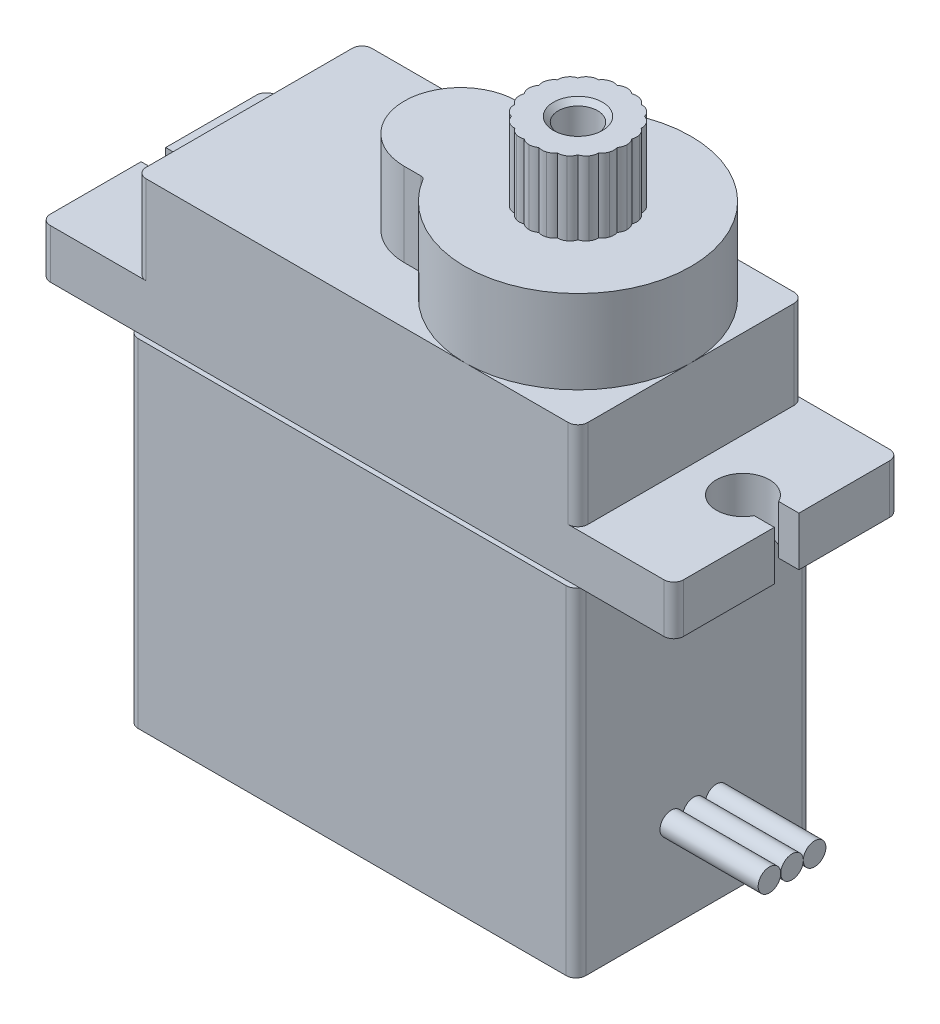
SolidWorks part; units mm, degrees
ref_plane "Ön Düzlem" through (0, 0, 0) normal (0, 0, 1) x (1, 0, 0)
ref_plane "Üst Düzlem" through (0, 0, 0) normal (0, 1, 0) x (1, 0, 0)
ref_plane "Sağ Düzlem" through (0, 0, 0) normal (1, 0, 0) x (0, 0, -1)
sketch "Sketch1" plane through (0, 0, 0) normal (0, 1, 0) x (1, 0, 0)
  line L1 (-11.4, -6) -> (11.4, -6)
  line L2 (-11.4, -6) -> (-11.4, 6)
  line L3 (-11.4, 6) -> (11.4, 6)
  line L4 (11.4, -6) -> (11.4, 6)
  line L5 (-11.4, -6) -> (11.4, 6) construction
  line L6 (-11.4, 6) -> (11.4, -6) construction
  point P0 (0, 0)
  dimension "D1" = 22.8
  dimension "D2" = 12
extrude "Boss-Extrude1" add sketch "Sketch1" along normal blind 17.2
sketch "Sketch2" plane through (0, 17.2, 0) normal (0, 1, 0) x (1, 0, 0)
  line L0 (-11.4, 6) -> (-11.4, -6) construction
  line L1 (-16.125, -5.75) -> (16.125, -5.75)
  line L2 (-16.125, -5.75) -> (-16.125, -0.625)
  line L3 (-16.125, 5.75) -> (16.125, 5.75)
  line L4 (16.125, -5.75) -> (16.125, -0.625)
  line L5 (-16.125, -5.75) -> (16.125, 5.75) construction
  line L6 (-16.125, 5.75) -> (16.125, -5.75) construction
  line L7 (0, -5.75) -> (0, 5.75) construction
  line L8 (-16.125, 0.625) -> (-16.125, 5.75)
  line L9 (-15.0966, 0.625) -> (-16.125, 0.625)
  line L10 (-15.0966, -0.625) -> (-16.125, -0.625)
  line L11 (-15.6108, 0.625) -> (-15.6108, -0.625) construction
  line L12 (15.0966, 0.625) -> (16.125, 0.625)
  line L13 (15.0966, -0.625) -> (16.125, -0.625)
  line L14 (16.125, 0.625) -> (16.125, 5.75)
  arc A0 (-15.0966, -0.625) -> (-15.0966, 0.625) centre (-13.9, 0) ccw
  arc A1 (15.0966, -0.625) -> (15.0966, 0.625) centre (13.9, 0) cw
  point P0 (0, 0)
  point P10 (-15.6108, 0)
  point P14 (0, 0)
  dimension "D5" = 2.7
  dimension "D1" = 11.5
  dimension "D2" = 32.25
  dimension "D3" = 4.725
  dimension "D4" = 2.5
  dimension "D6" = 1.25
extrude "Boss-Extrude2" add sketch "Sketch2" along normal blind 2.5
sketch "Sketch3" plane through (0, 19.7, 0) normal (0, 1, 0) x (1, 0, 0)
  line L0 (11.4, 5.75) -> (-11.4, 5.75) construction
  line L1 (-11.25, -5.75) -> (11.25, -5.75)
  line L2 (-11.25, -5.75) -> (-11.25, 5.75)
  line L3 (-11.25, 5.75) -> (11.25, 5.75)
  line L4 (11.25, -5.75) -> (11.25, 5.75)
  line L5 (-11.25, -5.75) -> (11.25, 5.75) construction
  line L6 (-11.25, 5.75) -> (11.25, -5.75) construction
  line L7 (-16.125, 5.75) -> (-16.125, 0.625) construction
  point P0 (0, 0)
  dimension "D1" = 22.5
  dimension "D2" = 4.875
extrude "Boss-Extrude3" add sketch "Sketch3" along normal blind 4.5
sketch "Sketch4" plane through (0, 24.2, 0) normal (0, 1, 0) x (1, 0, 0)
  line L0 (11.25, 5.75) -> (-11.25, 5.75) construction
  line L2 (-11.4, -5.75) -> (11.4, -5.75) construction
  line L4 (11.25, -5.75) -> (11.25, 5.75) construction
  line L5 (-0.475, 2.875) -> (0.378, 2.875)
  line L6 (-0.475, -2.875) -> (0.378, -2.875)
  arc A0 (0.5915, -2.9948) -> (0.5915, 2.9948) centre (5.5, 0) ccw
  arc A1 (-0.475, 2.875) -> (-0.475, -2.875) centre (-0.475, 0) ccw
  arc A2 (0.5915, -2.9948) -> (0.378, -2.875) centre (0.378, -3.125) ccw
  arc A3 (0.5915, 2.9948) -> (0.378, 2.875) centre (0.378, 3.125) cw
  dimension "D1" = 5.975
  dimension "D2" = 5.75
  dimension "D3" = 0.25
extrude "Boss-Extrude4" add sketch "Sketch4" along normal blind 4.25
sketch "Sketch5" plane through (0, 28.45, 0) normal (0, 1, 0) x (1, 0, 0)
  arc A1 (3.1357, 0.3745) -> (3.0053, 0) centre (3.5651, 0.015) ccw
  arc A2 (3.1357, -0.3745) -> (3.0053, 0) centre (3.5651, -0.015) cw
  circle A3 centre (5.5, 0) radius 2.375 construction
  arc A4 (3.3671, 1.0868) -> (3.1274, 0.7709) centre (3.6644, 0.6122) ccw
  arc A5 (3.1357, 0.3745) -> (3.1274, 0.7709) centre (3.6551, 0.5837) cw
  arc A6 (3.8073, 1.6927) -> (3.4817, 1.4664) centre (3.9434, 1.1495) ccw
  arc A7 (3.3671, 1.0868) -> (3.4817, 1.4664) centre (3.9258, 1.1252) cw
  arc A8 (4.4132, 2.1329) -> (4.0336, 2.0183) centre (4.3748, 1.5742) ccw
  arc A9 (3.8073, 1.6927) -> (4.0336, 2.0183) centre (4.3505, 1.5566) cw
  arc A10 (5.1255, 2.3643) -> (4.7291, 2.3726) centre (4.9163, 1.8449) ccw
  arc A11 (4.4132, 2.1329) -> (4.7291, 2.3726) centre (4.8878, 1.8356) cw
  arc A12 (5.8745, 2.3643) -> (5.5, 2.4947) centre (5.515, 1.9349) ccw
  arc A13 (5.1255, 2.3643) -> (5.5, 2.4947) centre (5.485, 1.9349) cw
  arc A14 (6.5868, 2.1329) -> (6.2709, 2.3726) centre (6.1122, 1.8356) ccw
  arc A15 (5.8745, 2.3643) -> (6.2709, 2.3726) centre (6.0837, 1.8449) cw
  arc A16 (7.1927, 1.6927) -> (6.9664, 2.0183) centre (6.6495, 1.5566) ccw
  arc A17 (6.5868, 2.1329) -> (6.9664, 2.0183) centre (6.6252, 1.5742) cw
  arc A18 (7.6329, 1.0868) -> (7.5183, 1.4664) centre (7.0742, 1.1252) ccw
  arc A19 (7.1927, 1.6927) -> (7.5183, 1.4664) centre (7.0566, 1.1495) cw
  arc A20 (7.8643, 0.3745) -> (7.8726, 0.7709) centre (7.3449, 0.5837) ccw
  arc A21 (7.6329, 1.0868) -> (7.8726, 0.7709) centre (7.3356, 0.6122) cw
  arc A22 (7.8643, -0.3745) -> (7.9947, 0) centre (7.4349, -0.015) ccw
  arc A23 (7.8643, 0.3745) -> (7.9947, 0) centre (7.4349, 0.015) cw
  arc A24 (7.6329, -1.0868) -> (7.8726, -0.7709) centre (7.3356, -0.6122) ccw
  arc A25 (7.8643, -0.3745) -> (7.8726, -0.7709) centre (7.3449, -0.5837) cw
  arc A26 (7.1927, -1.6927) -> (7.5183, -1.4664) centre (7.0566, -1.1495) ccw
  arc A27 (7.6329, -1.0868) -> (7.5183, -1.4664) centre (7.0742, -1.1252) cw
  arc A28 (6.5868, -2.1329) -> (6.9664, -2.0183) centre (6.6252, -1.5742) ccw
  arc A29 (7.1927, -1.6927) -> (6.9664, -2.0183) centre (6.6495, -1.5566) cw
  arc A30 (5.8745, -2.3643) -> (6.2709, -2.3726) centre (6.0837, -1.8449) ccw
  arc A31 (6.5868, -2.1329) -> (6.2709, -2.3726) centre (6.1122, -1.8356) cw
  arc A32 (5.1255, -2.3643) -> (5.5, -2.4947) centre (5.485, -1.9349) ccw
  arc A33 (5.8745, -2.3643) -> (5.5, -2.4947) centre (5.515, -1.9349) cw
  arc A34 (4.4132, -2.1329) -> (4.7291, -2.3726) centre (4.8878, -1.8356) ccw
  arc A35 (5.1255, -2.3643) -> (4.7291, -2.3726) centre (4.9163, -1.8449) cw
  arc A36 (3.8073, -1.6927) -> (4.0336, -2.0183) centre (4.3505, -1.5566) ccw
  arc A37 (4.4132, -2.1329) -> (4.0336, -2.0183) centre (4.3748, -1.5742) cw
  arc A38 (3.3671, -1.0868) -> (3.4817, -1.4664) centre (3.9258, -1.1252) ccw
  arc A39 (3.8073, -1.6927) -> (3.4817, -1.4664) centre (3.9434, -1.1495) cw
  arc A40 (3.1357, -0.3745) -> (3.1274, -0.7709) centre (3.6551, -0.5837) ccw
  arc A41 (3.3671, -1.0868) -> (3.1274, -0.7709) centre (3.6644, -0.6122) cw
  arc A82 (5.5, -5.75) -> (11.25, 0) centre (5.5, 0) ccw construction
  arc A83 (5.5, -5.75) -> (11.25, 0) centre (5.5, 0) ccw construction
  circle A84 centre (5.5, 0) radius 1
  point P106 (5.5, 0)
  dimension "D1" = 2
  dimension "D3" = 0.56
  dimension "D4" = 4.75
extrude "Boss-Extrude5" add sketch "Sketch5" along normal blind 3.75 separate body
chamfer "Chamfer1" distance 0.25 angle 45 1 edges at (5.5, 32.2, 1)
fillet "Fillet1" radius 0.5 12 edges at (-11.4, 8.6, -6) (-11.4, 8.6, 6) (11.4, 8.6, -6) (11.4, 8.6, 6) (11.25, 21.95, -5.75) (11.25, 21.95, 5.75) (-11.25, 21.95, 5.75) (-11.25, 21.95, -5.75) (-16.125, 18.45, -5.75) (-16.125, 18.45, 5.75) (16.125, 18.45, -5.75) (16.125, 18.45, 5.75)
sketch "Sketch7" plane through (11.4, 0, 0) normal (1, 0, 0) x (0, 0, -1)
  circle A0 centre (0, 4.55) radius 0.575
  circle A1 centre (1.15, 4.55) radius 0.575
  circle A2 centre (-1.15, 4.55) radius 0.575
  dimension "D2" = 1.15
  dimension "D1" = 4.55
extrude "Boss-Extrude6" add sketch "Sketch7" along normal blind 5 separate body contours A2 region at (11.4, 4.55, 1.15)
extrude "Boss-Extrude7" add sketch "Sketch7<3>" along normal blind 5 separate body contours A0 region at (11.4, 4.55, 0)
sketch "Sketch7<3>" plane through (11.4, 0, 0) normal (1, 0, 0) x (0, 0, -1) same geometry as "Sketch7"
extrude "Boss-Extrude8" add sketch "Sketch7<4>" along normal blind 5 separate body contours A1 region at (11.4, 4.55, -1.15)
sketch "Sketch7<4>" plane through (11.4, 0, 0) normal (1, 0, 0) x (0, 0, -1) same geometry as "Sketch7"
